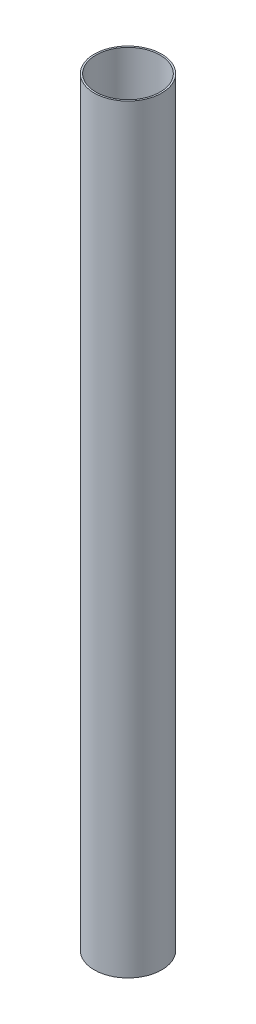
SolidWorks part; units mm, degrees
material "6063-T6"
ref_plane "Front Plane" through (0, 0, 0) normal (0, 0, 1) x (1, 0, 0)
ref_plane "Top Plane" through (0, 0, 0) normal (0, 1, 0) x (1, 0, 0)
ref_plane "Right Plane" through (0, 0, 0) normal (1, 0, 0) x (0, 0, -1)
sketch "Sketch1" plane through (0, 0, 0) normal (0, 1, 0) x (1, 0, 0)
  circle A0 centre (0, 0) radius 24.1554
  circle A1 centre (0, 0) radius 25.4
  dimension "D1" = 50.8
  dimension "D2" = 1.2446
extrude "body" add sketch "Sketch1" along normal blind 571.5
sketch "Sketch2" plane through (0, 0, 0) normal (0, 0, 1) x (1, 0, 0)
  line L0 (0, 0) -> (0, 28.2921) construction
  line L1 (-24.1554, 0) -> (24.1554, 0) construction
  line L2 (23.0187, 6.35) -> (24.892, 6.35)
  line L3 (23.0187, 6.35) -> (23.0187, 8.0772)
  line L4 (23.0187, 8.0772) -> (24.892, 8.0772)
  line L5 (24.892, 6.35) -> (24.892, 8.0772)
  dimension "D1" = 46.0375
  dimension "D2" = 49.784
  dimension "D3" = 1.7272
  dimension "D4" = 6.35
revolve "Cut-Revolve1" cut sketch "Sketch2" angle 360 about L0
